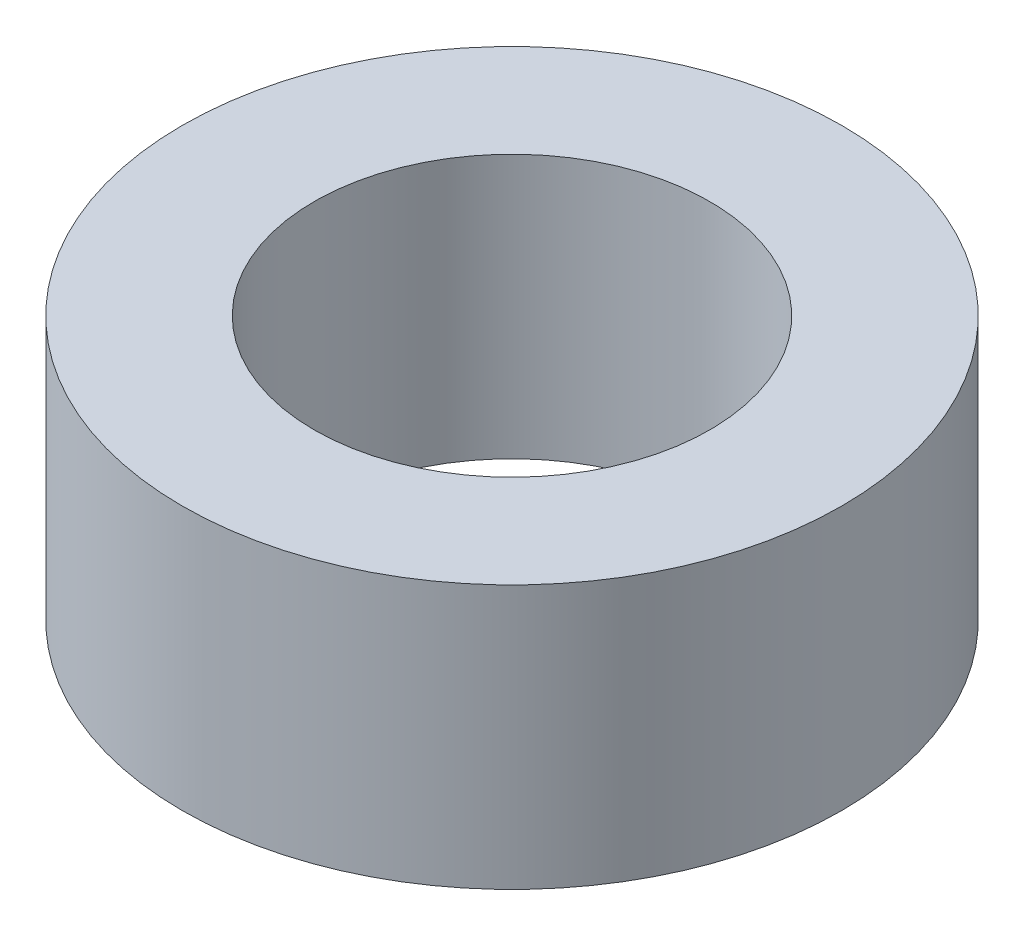
SolidWorks part; units mm, degrees
ref_plane "Front Plane" through (0, 0, 0) normal (0, 0, 1) x (1, 0, 0)
ref_plane "Top Plane" through (0, 0, 0) normal (0, 1, 0) x (1, 0, 0)
ref_plane "Right Plane" through (0, 0, 0) normal (1, 0, 0) x (0, 0, -1)
sketch "Sketch1" plane through (0, 0, 0) normal (0, 1, 0) x (1, 0, 0)
  circle A0 centre (0, 0) radius 25
  dimension "FLANGE_OD" = 50
extrude "Boss-Extrude1" add sketch "Sketch1" along normal blind 20
sketch "Sketch2" plane through (0, 0, 0) normal (0, 1, 0) x (1, 0, 0)
  circle A0 centre (0, 0) radius 15
  dimension "BORE_D" = 30
extrude "Cut-Extrude1" cut sketch "Sketch2" along normal through all
sketch "Sketch3" plane through (0, 20, 0) normal (0, 1, 0) x (1, 0, 0)
  circle A0 centre (0, 0) radius 9.0267 construction
  circle A1 centre (-9.0267, 0) radius 1.6992
  dimension "BOLT_D" = 3.3984
  dimension "BOLT_PCD" = 18.0534
extrude "Cut-Extrude2" cut sketch "Sketch3" against normal blind 17.3323 rebuild error yes
pattern_circular "CirPattern1" count 6 over 360 rebuild error yes
